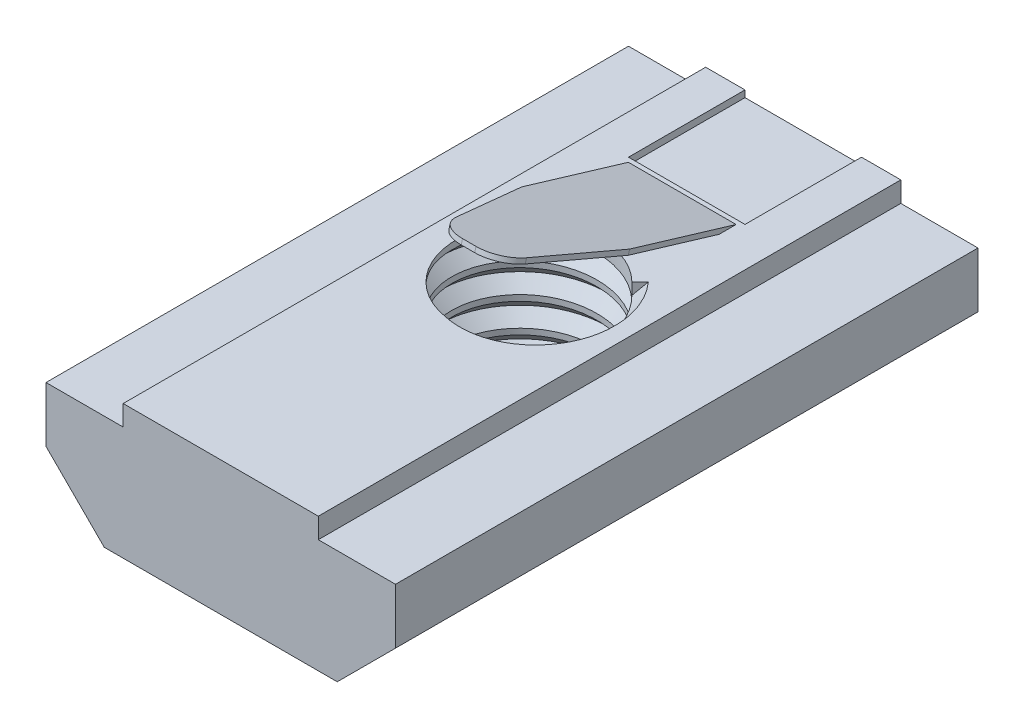
SolidWorks part; units mm, degrees
ref_plane "前视基准面" through (0, 0, 0) normal (0, 0, 1) x (1, 0, 0)
ref_plane "上视基准面" through (0, 0, 0) normal (0, 1, 0) x (1, 0, 0)
ref_plane "右视基准面" through (0, 0, 0) normal (1, 0, 0) x (0, 0, -1)
sketch "草图1" plane through (0, 0, 0) normal (0, 0, 1) x (1, 0, 0)
  line L0 (-6, 0) -> (6, 0)
  line L1 (-6, 0) -> (-6, 3.9)
  line L2 (-6, 3.9) -> (-3.35, 3.9)
  line L3 (-3.35, 3.9) -> (-3.35, 4.6)
  line L4 (-3.35, 4.6) -> (3.35, 4.6)
  line L5 (3.35, 4.6) -> (3.35, 3.9)
  line L6 (3.35, 3.9) -> (6, 3.9)
  line L7 (6, 3.9) -> (6, 0)
  point P6 (0, 4.6)
  dimension "D1" = 12
  dimension "D2" = 3.9
  dimension "D3" = 3.9
  dimension "D4" = 0.7
  dimension "D5" = 6.7
extrude "凸台-拉伸1" add sketch "草图1" along normal blind 20
chamfer "倒角1" distance 2 angle 45 2 edges at (6, 0, 10) (-6, 0, 10)
sketch "草图2" plane through (0, 4.6, 0) normal (0, 1, 0) x (1, 0, 0)
  circle A0 centre (0, -9.419) radius 2.5
  dimension "D1" = 5
extrude "切除-拉伸1" cut sketch "草图2" against normal through all
sketch "草图4" plane through (0, 4.6, 0) normal (0, 1, 0) x (1, 0, 0)
  circle A0 centre (0, -9.419) radius 2.5 construction
  circle A1 centre (0, -9.419) radius 2.5
curve "螺旋线/涡状线1" pitch 1 height 5 radius 2.5 centre (0, 4.6, 9.419) axis (0, -1, 0) start towards (0.7071, 0, -0.7071)
sketch "草图5" plane through (0, 0, 0) normal (1, 0, 0) x (0, 0, -1)
  line L0 (-6.919, 1.125) -> (-6.919, 0.325)
  line L1 (-6.919, 0.725) -> (-6.519, 0.725) construction
  line L2 (-6.919, 1.125) -> (-6.519, 0.725)
  line L3 (-6.519, 0.725) -> (-6.919, 0.325)
  dimension "D1" = 0.8
  dimension "D2" = 0.4
sweep "切除-扫描1" cut profiles "草图5" path "螺旋线/涡状线1"
sketch "草图6" plane through (0, 0, 0) normal (0, 0, -1) x (-1, 0, 0)
  line L0 (-3.35, 4.6) -> (3.35, 4.6) construction
  line L1 (2, 4.8305) -> (-2, 4.8305)
  line L2 (2, 4.8305) -> (2, 4.3695)
  line L3 (2, 4.3695) -> (-2, 4.3695)
  line L4 (-2, 4.8305) -> (-2, 4.3695)
  line L5 (2, 4.8305) -> (-2, 4.3695) construction
  line L6 (2, 4.3695) -> (-2, 4.8305) construction
  point P0 (0, 4.6)
  dimension "D1" = 4
extrude "切除-拉伸2" cut sketch "草图6" against normal blind 4
sketch "草图7" plane through (0, 0, 0) normal (1, 0, 0) x (0, 0, -1)
  line L0 (-4.1543, 4.6) -> (-11.4661, 6.7959)
  line L1 (-20, 4.6) -> (0, 4.6) construction
  line L2 (-11.4661, 6.7959) -> (-11.5145, 6.6344)
  line L3 (-11.5145, 6.6344) -> (-4.7404, 4.6)
  line L4 (-4.7404, 4.6) -> (-4.1543, 4.6)
extrude "凸台-拉伸2" add sketch "草图7" along normal blind 1.85 and the other way blind 1.85
sketch "草图8" plane through (0, 3.075, -0.9235) normal (0, 0.9577, -0.2876) x (1, 0, 0)
  line L0 (-1.85, -9.119) -> (-1.0412, -12.9362)
  line L1 (-1.85, -5.3018) -> (-1.85, -12.9362) construction
  line L2 (-1.0412, -12.9362) -> (-1.85, -12.9362)
  line L3 (-1.85, -12.9362) -> (-1.85, -9.119)
extrude "切除-拉伸3" cut sketch "草图8" against normal blind 1.85
mirror "镜向1" about plane through (0, 0, 0) normal (1, 0, 0) of "切除-拉伸3"
fillet "圆角1" radius 1 2 edges at (1.0412, 6.7151, 11.4903) (-1.0412, 6.7151, 11.4903)
